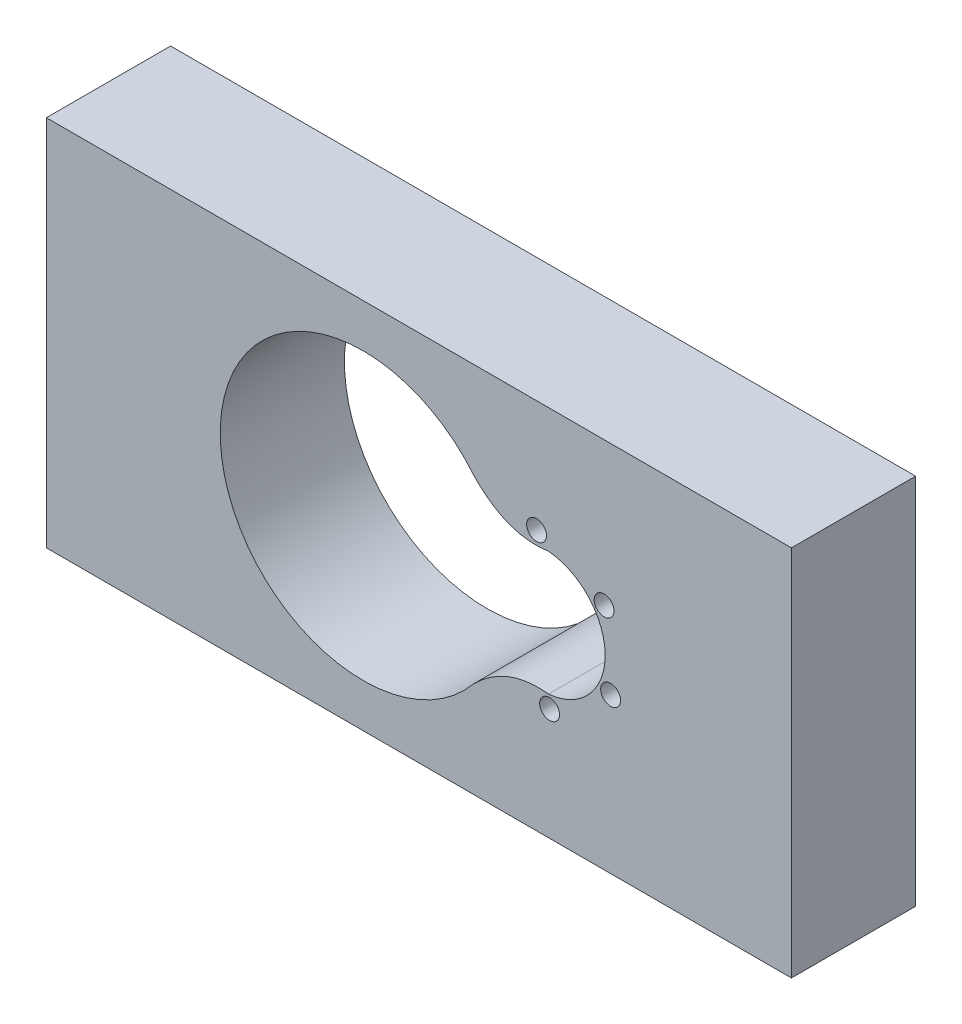
SolidWorks part; units mm, degrees
ref_plane "Plan de face" through (0, 0, 0) normal (0, 0, 1) x (1, 0, 0)
ref_plane "Plan de dessus" through (0, 0, 0) normal (0, 1, 0) x (1, 0, 0)
ref_plane "Plan de droite" through (0, 0, 0) normal (1, 0, 0) x (0, 0, -1)
sketch "Esquisse1" plane through (0, 0, 0) normal (0, 0, 1) x (1, 0, 0)
  line L1 (0, 0) -> (60, 0)
  line L2 (0, 0) -> (0, 30)
  line L3 (0, 30) -> (60, 30)
  line L4 (60, 0) -> (60, 30)
  dimension "D1" = 30
  dimension "D2" = 60
extrude "Boss.-Extru.1" add sketch "Esquisse1" along normal blind 10
sketch "Esquisse2" plane through (0, 0, 10) normal (0, 0, 1) x (1, 0, 0)
  line L0 (66.0915, 15) -> (-1.5751, 15) construction
  line L1 (40, 34.4565) -> (40, -6.8023) construction
  line L2 (60, 30) -> (0, 30) construction
  line L3 (60, 0) -> (60, 30) construction
  arc A0 (40.4408, 19.9805) -> (40.4406, 10.0195) centre (40, 15) cw
  circle A2 centre (39.4746, 20.9769) radius 0.8
  circle A3 centre (44.9135, 18.4435) radius 0.8
  circle A4 centre (45.4389, 12.4666) radius 0.8
  circle A5 centre (40.5254, 9.0231) radius 0.8
  arc A6 (34.3574, 22.3346) -> (34.3761, 7.688) centre (25.5, 15) ccw
  circle A8 centre (34.5611, 17.5334) radius 0.8 [skipped]
  circle A9 centre (35.0865, 11.5565) radius 0.8 [skipped]
  spline S0 degree 2 poles (34.3574, 22.3346) (37.032, 19.4585) (40.4408, 19.9805) knots 0 0 0 1 1 1
  spline S1 degree 2 poles (34.3761, 7.688) (37.0756, 10.41) (40.4406, 10.0195) knots 0 0 0 1 1 1
  point P18 (40, 15)
  dimension "D1" = 11.5
  dimension "D2" = 5
  dimension "D3" = 1.6
  dimension "D5" = 14.5
  dimension "D6" = 15
  dimension "D7" = 20
  dimension "D4" = 6
extrude "Enlèv. mat.-Extru.1" cut sketch "Esquisse2" against normal through all
